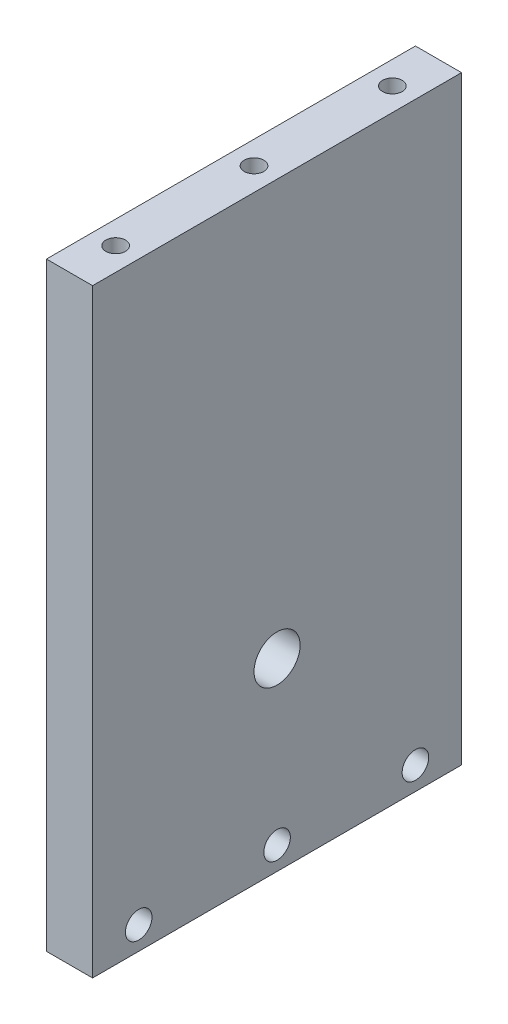
SolidWorks part; units mm, degrees
ref_plane "Front Plane" through (0, 0, 0) normal (0, 0, 1) x (1, 0, 0)
ref_plane "Top Plane" through (0, 0, 0) normal (0, 1, 0) x (1, 0, 0)
ref_plane "Right Plane" through (0, 0, 0) normal (1, 0, 0) x (0, 0, -1)
sketch "Sketch1" plane through (0, 0, 0) normal (1, 0, 0) x (0, 0, -1)
  line L1 (0, 0) -> (-50.8, 0)
  line L2 (0, 0) -> (0, 82.55)
  line L3 (0, 82.55) -> (-50.8, 82.55)
  line L4 (-50.8, 0) -> (-50.8, 82.55)
  dimension "D1" = 82.55
  dimension "D2" = 50.8
extrude "Boss-Extrude1" add sketch "Sketch1" along normal blind 6.35
sketch "Sketch2" plane through (0, 82.55, 0) normal (0, 1, 0) x (1, 0, 0)
  line L0 (0, 0) -> (0, -50.8) construction
  line L1 (6.35, -50.8) -> (0, -50.8) construction
  circle A0 centre (3.175, -44.45) radius 1.7526
  circle A1 centre (3.175, -6.35) radius 1.7526
  circle A3 centre (3.175, -25.4) radius 1.7526
  dimension "D1" = 3.5052
  dimension "D3" = 3.5052
  dimension "D5" = 3.5052
  dimension "D2" = 3.175
  dimension "D4" = 6.35
  dimension "D6" = 25.4
  dimension "D7" = 44.45
sketch "Sketch3" plane through (6.35, 0, 0) normal (1, 0, 0) x (0, 0, -1)
  line L0 (-50.8, 82.55) -> (-50.8, 0) construction
  line L1 (-50.8, 0) -> (0, 0) construction
  circle A0 centre (-44.45, 3.175) radius 1.8288
  circle A1 centre (-25.4, 3.175) radius 1.8288
  circle A2 centre (-6.35, 3.175) radius 1.8288
  dimension "D7" = 3.6576
  dimension "D8" = 3.6576
  dimension "D9" = 3.6576
  dimension "D1" = 6.35
  dimension "D2" = 25.4
  dimension "D3" = 44.45
  dimension "D4" = 3.175
  dimension "D5" = 3.175
  dimension "D6" = 3.175
extrude "Cut-Extrude1" cut sketch "Sketch3" against normal blind 6.35
hole_wizard "#6-32 Tapped Hole1" positions "Sketch10" profile "Sketch11" tap size "#6-32" standard "ANSI Inch"
sketch "Sketch10" plane through (0, 82.55, 0) normal (0, 1, 0) x (1, 0, 0)
  point P0 (3.175, -6.35)
  point P3 (3.175, -25.4)
  point P6 (3.175, -44.45)
sketch "Sketch11" plane through (3.175, 82.55, 6.35) normal (1, 0, 0) x (0, 0, 1)
  line L0 (0, 0) -> (0, 12.7)
  line L1 (0, 12.7) -> (1.3525, 11.8873)
  line L2 (1.3525, 11.8873) -> (1.3525, 0)
  line L5 (1.3525, 0) -> (0, 0)
  line L10 (0, 12.7) -> (-1.3526, 11.8873) construction
  line L11 (0, -6.35) -> (0, 107.95) construction
  dimension "Tap Drill Dia." = 2.7051
  dimension "Tap Drill Depth" = 12.7
  dimension "Drill Angle" = 118
cosmetic thread "Hole Thread1" parameters "D1"=10.16, "D2"=3.5052
cosmetic thread "Hole Thread2" parameters "D1"=10.16, "D2"=3.5052
cosmetic thread "Hole Thread3" parameters "D1"=10.16, "D2"=3.5052
sketch "Sketch12" plane through (6.35, 0, 0) normal (1, 0, 0) x (0, 0, -1)
  line L0 (-50.8, 0) -> (0, 0) construction
  line L1 (-50.8, 82.55) -> (-50.8, 0) construction
  circle A0 centre (-25.4, 25.4) radius 3.175
  dimension "D1" = 6.35
  dimension "D2" = 25.4
  dimension "D3" = 25.4
extrude "Cut-Extrude3" cut sketch "Sketch12" against normal blind 6.35
